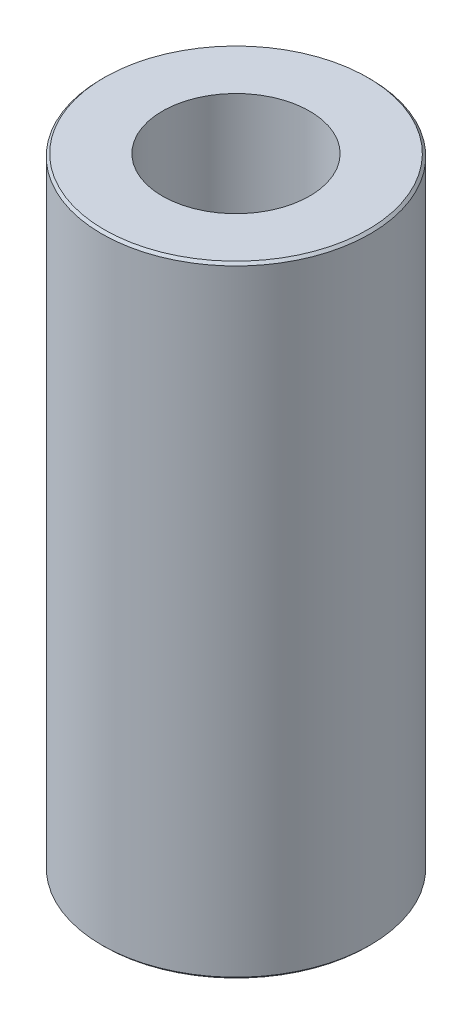
SolidWorks part; units mm, degrees
ref_plane "Front Plane" through (0, 0, 0) normal (0, 0, 1) x (1, 0, 0)
ref_plane "Top Plane" through (0, 0, 0) normal (0, 1, 0) x (1, 0, 0)
ref_plane "Right Plane" through (0, 0, 0) normal (1, 0, 0) x (0, 0, -1)
sketch "Sketch1" plane through (0, 0, 0) normal (0, 1, 0) x (1, 0, 0)
  circle A0 centre (0, 0) radius 40
  dimension "SHAFT_OD" = 80
extrude "Boss-Extrude1" add sketch "Sketch1" along normal blind 185.0143
sketch "Sketch2" plane through (0, 0, 0) normal (0, 1, 0) x (1, 0, 0)
  circle A0 centre (0, 0) radius 21.9495
  dimension "BORE_D" = 43.8989
extrude "Cut-Extrude1" cut sketch "Sketch2" along normal through all
chamfer "Chamfer1" distance 0.7284 angle 45 2 edges at (0, 185.0143, 40) (0, 0, 40)
